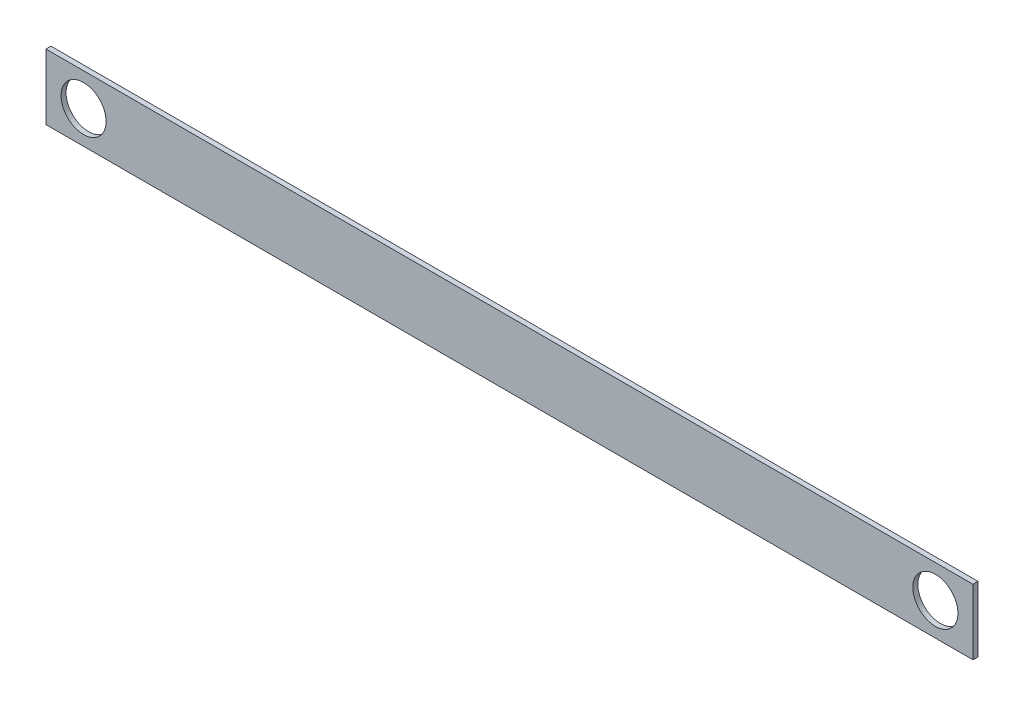
SolidWorks part; units mm, degrees
ref_plane "Front Plane" through (0, 0, 0) normal (0, 0, 1) x (1, 0, 0)
ref_plane "Top Plane" through (0, 0, 0) normal (0, 1, 0) x (1, 0, 0)
ref_plane "Right Plane" through (0, 0, 0) normal (1, 0, 0) x (0, 0, -1)
sketch "Sketch1" plane through (0, 0, 0) normal (0, 0, 1) x (1, 0, 0)
  line L1 (-124.7191, 20.1926) -> (245.2809, 20.1926)
  line L2 (-124.7191, 20.1926) -> (-124.7191, -5.939)
  line L3 (-124.7191, -5.939) -> (245.2809, -5.939)
  line L4 (245.2809, 20.1926) -> (245.2809, -5.939)
  dimension "D1" = 370
extrude "Boss-Extrude1" add sketch "Sketch1" along normal blind 2
sketch "Sketch2" plane through (0, 0, 2) normal (0, 0, 1) x (1, 0, 0)
  line L0 (-124.7191, 7.1268) -> (245.2809, 7.1268) construction
  line L1 (-124.7191, 20.1926) -> (-124.7191, -5.939) construction
  line L2 (245.2809, -5.939) -> (245.2809, 20.1926) construction
  circle A0 centre (-109.7191, 7.1268) radius 9
  circle A1 centre (230.2809, 7.1268) radius 9
  dimension "D1" = 15
  dimension "D2" = 15
extrude "Cut-Extrude1" cut sketch "Sketch2" against normal blind 2 contours A0
extrude "Cut-Extrude2" cut sketch "Sketch2<4>" against normal blind 2
sketch "Sketch2<4>" plane through (0, 0, 2) normal (0, 0, 1) x (1, 0, 0) same geometry as "Sketch2"
